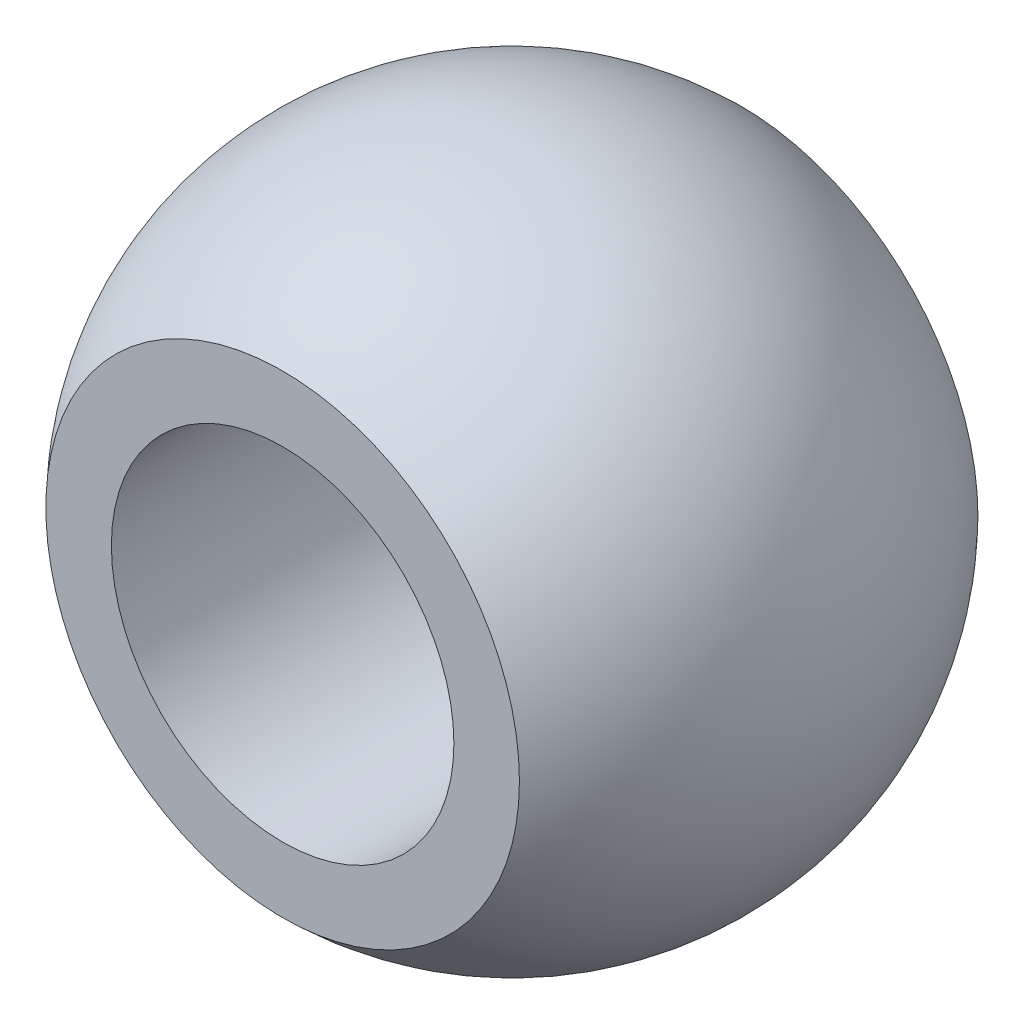
SolidWorks part; units mm, degrees
ref_plane "Front Plane" through (0, 0, 0) normal (0, 0, 1) x (1, 0, 0)
ref_plane "Top Plane" through (0, 0, 0) normal (0, 1, 0) x (1, 0, 0)
ref_plane "Right Plane" through (0, 0, 0) normal (1, 0, 0) x (0, 0, -1)
sketch "Sketch1" plane through (0, 0, 0) normal (0, 1, 0) x (1, 0, 0)
  line L0 (0, -8.4003) -> (0, 8.4003) construction
  line L1 (0, 9.165) -> (0, -9.165)
  arc A0 (0, 9.165) -> (0, -9.165) centre (0, 0) ccw
  dimension "D1" = 18.33
revolve "Revolve1" add sketch "Sketch1" angle 360 about L1
sketch "Sketch2" plane through (0, 0, 0) normal (0, 0, 1) x (1, 0, 0)
  circle A0 centre (0, 0) radius 4.7625
extrude "Cut-Extrude1" cut sketch "Sketch2" against normal through all and the other way through all
sketch "Sketch3" plane through (0, 0, 0) normal (1, 0, 0) x (0, 0, -1)
  line L5 (-7.8304, -4.7625) -> (-7.8304, 4.7625) construction
  line L6 (-9.2859, -6.5846) -> (-6.375, -6.5846)
  line L7 (-9.2859, -6.5846) -> (-9.2859, 6.5846)
  line L12 (-9.2859, 6.5846) -> (-6.375, 6.5846)
  line L13 (-6.375, -6.5846) -> (-6.375, 6.5846)
  line L14 (-9.2859, -6.5846) -> (-6.375, 6.5846) construction
  line L15 (-9.2859, 6.5846) -> (-6.375, -6.5846) construction
  line L16 (7.8304, -4.7625) -> (7.8304, 4.7625) construction
  line L17 (6.375, -6.5846) -> (9.2859, -6.5846)
  line L18 (6.375, -6.5846) -> (6.375, 6.5846)
  line L19 (6.375, 6.5846) -> (9.2859, 6.5846)
  line L20 (9.2859, -6.5846) -> (9.2859, 6.5846)
  line L21 (6.375, -6.5846) -> (9.2859, 6.5846) construction
  line L22 (6.375, 6.5846) -> (9.2859, -6.5846) construction
  arc A1 (7.8304, 4.7625) -> (-7.8304, 4.7625) centre (0, 0) ccw construction
  point P0 (-7.8304, 0)
  point P7 (7.8304, 0)
  point P14 (6.4357, 6.5253)
  point P18 (-6.2812, 6.6741)
  dimension "D1" = 12.75
extrude "Cut-Extrude2" cut sketch "Sketch3" against normal through all and the other way through all
